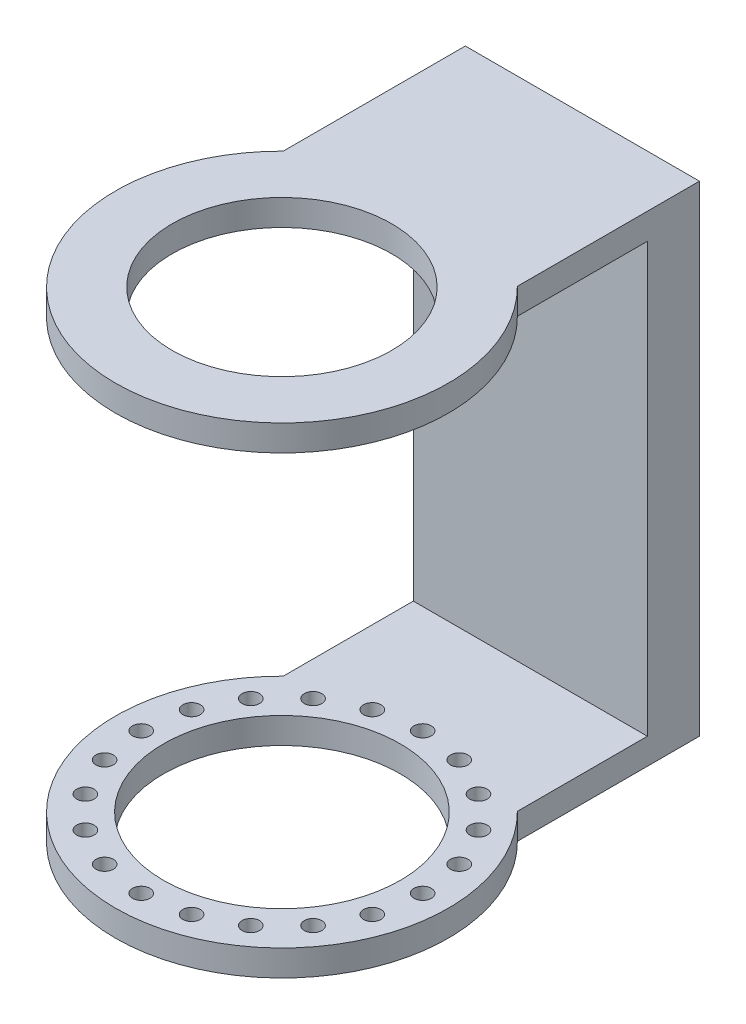
SolidWorks part; units mm, degrees
ref_plane "Front Plane" through (0, 0, 0) normal (0, 0, 1) x (1, 0, 0)
ref_plane "Top Plane" through (0, 0, 0) normal (0, 1, 0) x (1, 0, 0)
ref_plane "Right Plane" through (0, 0, 0) normal (1, 0, 0) x (0, 0, -1)
sketch "Sketch1" plane through (0, 0, 0) normal (0, 1, 0) x (1, 0, 0)
  circle A0 centre (0, 0) radius 27.05 construction
  circle A6 centre (0, -27.05) radius 1.675
  circle A21 centre (0, 0) radius 32
  circle A22 centre (-8.3589, -25.7261) radius 1.675
  circle A23 centre (-15.8996, -21.8839) radius 1.675
  circle A24 centre (-21.8839, -15.8996) radius 1.675
  circle A25 centre (-25.7261, -8.3589) radius 1.675
  circle A26 centre (-27.05, 0) radius 1.675
  circle A27 centre (-25.7261, 8.3589) radius 1.675
  circle A28 centre (-21.8839, 15.8996) radius 1.675
  circle A29 centre (-15.8996, 21.8839) radius 1.675
  circle A30 centre (-8.3589, 25.7261) radius 1.675
  circle A31 centre (0, 27.05) radius 1.675
  circle A32 centre (8.3589, 25.7261) radius 1.675
  circle A33 centre (15.8996, 21.8839) radius 1.675
  circle A34 centre (21.8839, 15.8996) radius 1.675
  circle A35 centre (25.7261, 8.3589) radius 1.675
  circle A36 centre (27.05, 0) radius 1.675
  circle A37 centre (25.7261, -8.3589) radius 1.675
  circle A38 centre (21.8839, -15.8996) radius 1.675
  circle A39 centre (15.8996, -21.8839) radius 1.675
  circle A40 centre (8.3589, -25.7261) radius 1.675
  dimension "D1" = 64
  dimension "D2" = 54.1
  dimension "D3" = 3.35
  dimension "D4" = 20
extrude "Boss-Extrude1" add sketch "Sketch1" along normal blind 5
sketch "Sketch2" plane through (0, 5, 0) normal (0, 1, 0) x (1, 0, 0)
  circle A0 centre (0, 0) radius 22.75
  dimension "D1" = 45.5
extrude "Cut-Extrude1" cut sketch "Sketch2" against normal through all
sketch "Sketch3" plane through (0, 0, 0) normal (0, 1, 0) x (1, 0, 0)
  line L0 (-22.5, 57.7541) -> (-22.5, 22.7541)
  line L1 (-22.5, 57.7541) -> (22.5, 57.7541)
  line L2 (22.5, 57.7541) -> (22.5, 22.7541)
  circle A0 centre (0, 0) radius 32 construction
  arc A1 (22.5, 22.7541) -> (-22.5, 22.7541) centre (0, 0) ccw
  point P6 (0, 57.7541)
  point P11 (23.1479, 22.0947)
  dimension "D1" = 45
  dimension "D2" = 35
extrude "Boss-Extrude2" add sketch "Sketch3" along normal up to surface (5 mm away) up to face at (0, 5, 22.75)
sketch "Sketch5" plane through (0, 5, 0) normal (0, 1, 0) x (1, 0, 0)
  line L0 (22.5, 22.7541) -> (22.5, 57.7541) construction
  line L1 (-22.5, 57.7541) -> (22.5, 57.7541)
  line L2 (-22.5, 57.7541) -> (-22.5, 47.7541)
  line L3 (-22.5, 47.7541) -> (22.5, 47.7541)
  line L4 (22.5, 57.7541) -> (22.5, 47.7541)
  dimension "D1" = 10
extrude "Boss-Extrude3" add sketch "Sketch5" along normal blind 82.4
sketch "Sketch7" plane through (0, 87.4, 0) normal (0, 1, 0) x (1, 0, 0)
  line L0 (-22.5, 22.7541) -> (-22.5, 57.7541)
  line L1 (-22.5, 57.7541) -> (22.5, 57.7541)
  line L2 (22.5, 57.7541) -> (22.5, 22.7541)
  arc A0 (-22.5, 22.7541) -> (22.5, 22.7541) centre (0, 0) ccw
extrude "Boss-Extrude6" add sketch "Sketch7" along normal blind 5
sketch "Sketch8" plane through (0, 92.4, 0) normal (0, 1, 0) x (1, 0, 0)
  circle A0 centre (0, 0) radius 21.1
  dimension "D1" = 42.2
extrude "Cut-Extrude3" cut sketch "Sketch8" against normal up to surface (5 mm away) up to face at (0, 87.4, -21.5656)
